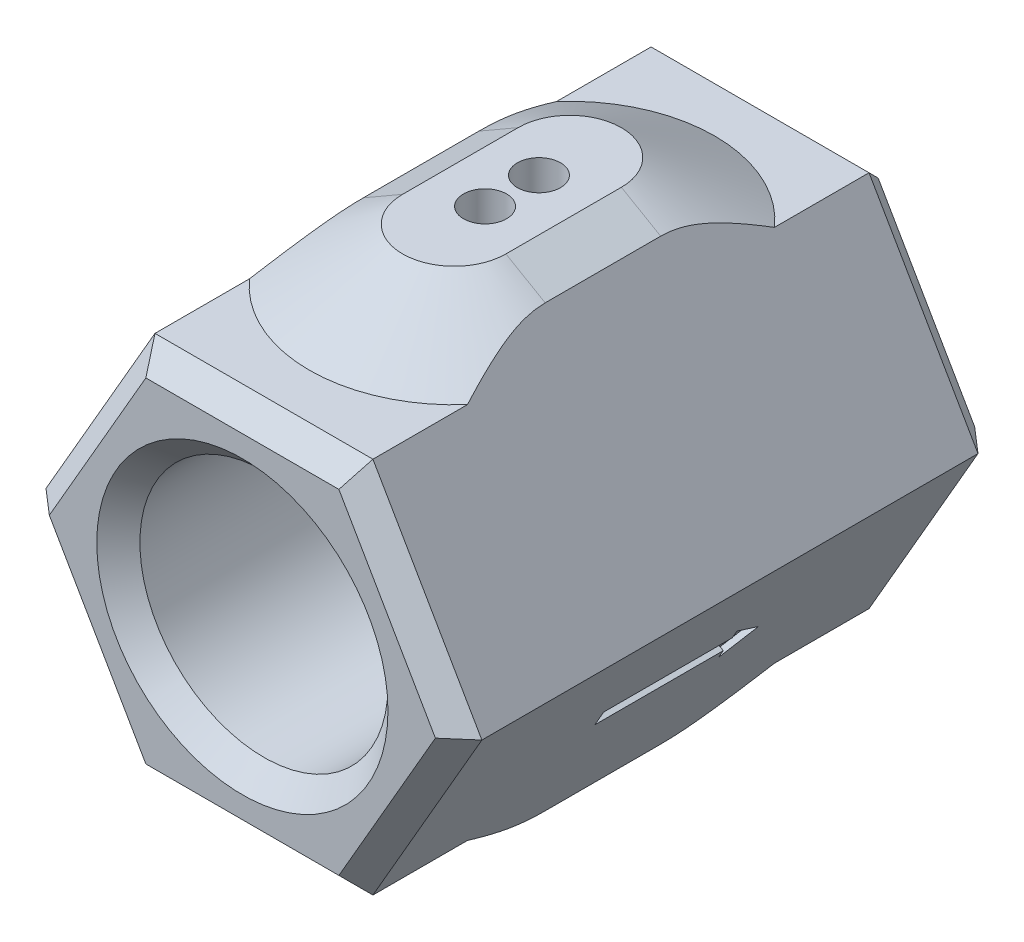
SolidWorks part; units mm, degrees
ref_plane "Front Plane" through (0, 0, 0) normal (0, 0, 1) x (1, 0, 0)
ref_plane "Top Plane" through (0, 0, 0) normal (0, 1, 0) x (1, 0, 0)
ref_plane "Right Plane" through (0, 0, 0) normal (1, 0, 0) x (0, 0, -1)
sketch "Sketch1" plane through (0, 0, 0) normal (0, 0, 1) x (1, 0, 0)
  line L1 (10.1036, 17.5) -> (-10.1036, 17.5)
  line L2 (-10.1036, 17.5) -> (-20.2073, 0)
  line L3 (-20.2073, 0) -> (-10.1036, -17.5)
  line L4 (-10.1036, -17.5) -> (10.1036, -17.5)
  line L5 (10.1036, -17.5) -> (20.2073, 0)
  line L6 (20.2073, 0) -> (10.1036, 17.5)
  circle A1 centre (0, 0) radius 17.5 construction
  dimension "D1" = 35
extrude "Boss-Extrude1" add sketch "Sketch1" along normal mid plane 50
sketch "Sketch2" plane through (0, 17.5, 0) normal (0, 1, 0) x (1, 0, 0)
  line L0 (0, -5.3538) -> (0, 5.3538) construction
  line L1 (-4.7885, -5.3538) -> (-4.7885, 5.3538)
  line L2 (4.7885, -5.3538) -> (4.7885, 5.3538)
  arc A0 (-4.7885, -5.3538) -> (4.7885, -5.3538) centre (0, -5.3538) ccw
  arc A1 (4.7885, 5.3538) -> (-4.7885, 5.3538) centre (0, 5.3538) ccw
  point P2 (0, 0)
extrude "Boss-Extrude2" add sketch "Sketch2" along normal blind 5 and the other way blind 40
sketch "Sketch6" plane through (0, 22.5, 0) normal (0, 1, 0) x (1, 0, 0)
  line L0 (0, 0) -> (0, -3.1794) construction
  line L1 (0, 0) -> (3.0445, 0) construction
  circle A0 centre (0, -2.5) radius 2
  circle A1 centre (0, 2.5) radius 2
  point P6 (0, -2.6837)
  dimension "D1" = 2.5
  dimension "D2" = 4
extrude "Cut-Extrude2" cut sketch "Sketch6" against normal through all
sketch "Sketch7" plane through (0, 0, -25) normal (0, 0, -1) x (-1, 0, 0)
  circle A0 centre (0, 0) radius 11.5
  dimension "D1" = 23
extrude "Cut-Extrude3" cut sketch "Sketch7" against normal through all
chamfer "Chamfer3" distance 2 angle 45 14 edges at (-11.5, 0, -25) (-11.5, 0, 25) (-15.1554, -8.75, 25) (-15.1554, 8.75, 25) (0, 17.5, 25) (0, -17.5, 25) (15.1554, 8.75, 25) (15.1554, -8.75, 25) (-15.1554, 8.75, -25) (-15.1554, -8.75, -25) (0, -17.5, -25) (15.1554, -8.75, -25) (0, 17.5, -25) (15.1554, 8.75, -25)
chamfer "Chamfer4" distance 5 angle 60 8 edges at (4.7885, -17.5, 0) (0, -17.5, -10.1423) (0, -17.5, 10.1423) (-4.7885, -17.5, 0) (-4.7885, 17.5, 0) (0, 17.5, 10.1423) (0, 17.5, -10.1423) (4.7885, 17.5, 0) first distance on face at (4.7885, -20, 0) first distance on face at (0, -20, -7.748) first distance on face at (0, -20, 7.748) first distance on face at (-4.7885, -20, 0) first distance on face at (-4.7885, 20, 0) first distance on face at (0, 20, 7.748) first distance on face at (0, 20, -7.748) first distance on face at (4.7885, 20, 0)
sketch "Sketch8" plane through (15.1554, -8.75, 0) normal (0.866, -0.5, 0) x (0, 0, -1)
  line L0 (4.8629, 0.8109) -> (4.8629, 1.6892)
  line L1 (-7.0552, -0.8582) -> (4.8629, -0.8582)
  line L2 (-7.0552, -0.8582) -> (-7.0552, 0.8109)
  line L3 (-7.0552, 0.8109) -> (4.8629, 0.8109)
  line L5 (-7.0552, -0.8582) -> (4.8629, 0.8109) construction
  line L6 (-7.0552, 0.8109) -> (4.8629, -0.8582) construction
  line L7 (4.8629, 1.6892) -> (7.7144, -0.0236)
  line L10 (-1.0961, -0.0236) -> (7.7144, -0.0236) construction
  line L11 (4.8629, -0.8582) -> (4.8629, -1.7364)
  line L12 (4.8629, -1.7364) -> (7.7144, -0.0236)
  point P0 (-1.0961, -0.0236)
sketch "Sketch9" plane through (-15.1554, 8.75, 0) normal (-0.866, 0.5, 0) x (0, 0, 1)
  line L0 (-4.5159, -0.8345) -> (-4.5159, -1.7128)
  line L1 (7.4022, 0.8345) -> (-4.5159, 0.8345)
  line L2 (7.4022, 0.8345) -> (7.4022, -0.8345)
  line L3 (7.4022, -0.8345) -> (-4.5159, -0.8345)
  line L4 (7.4022, 0.8345) -> (-4.5159, -0.8345) construction
  line L5 (7.4022, -0.8345) -> (-4.5159, 0.8345) construction
  line L6 (-4.5159, -1.7128) -> (-7.3674, 0)
  line L7 (1.4431, 0) -> (-7.3674, 0) construction
  line L8 (-4.5159, 0.8345) -> (-4.5159, 1.7128)
  line L9 (-4.5159, 1.7128) -> (-7.3674, 0)
  point P0 (1.4431, 0)
extrude "Cut-Extrude4" cut sketch "Sketch8" against normal blind 0.5
extrude "Cut-Extrude5" cut sketch "Sketch9" against normal blind 0.5
equation "\"2mmm\"=3"
